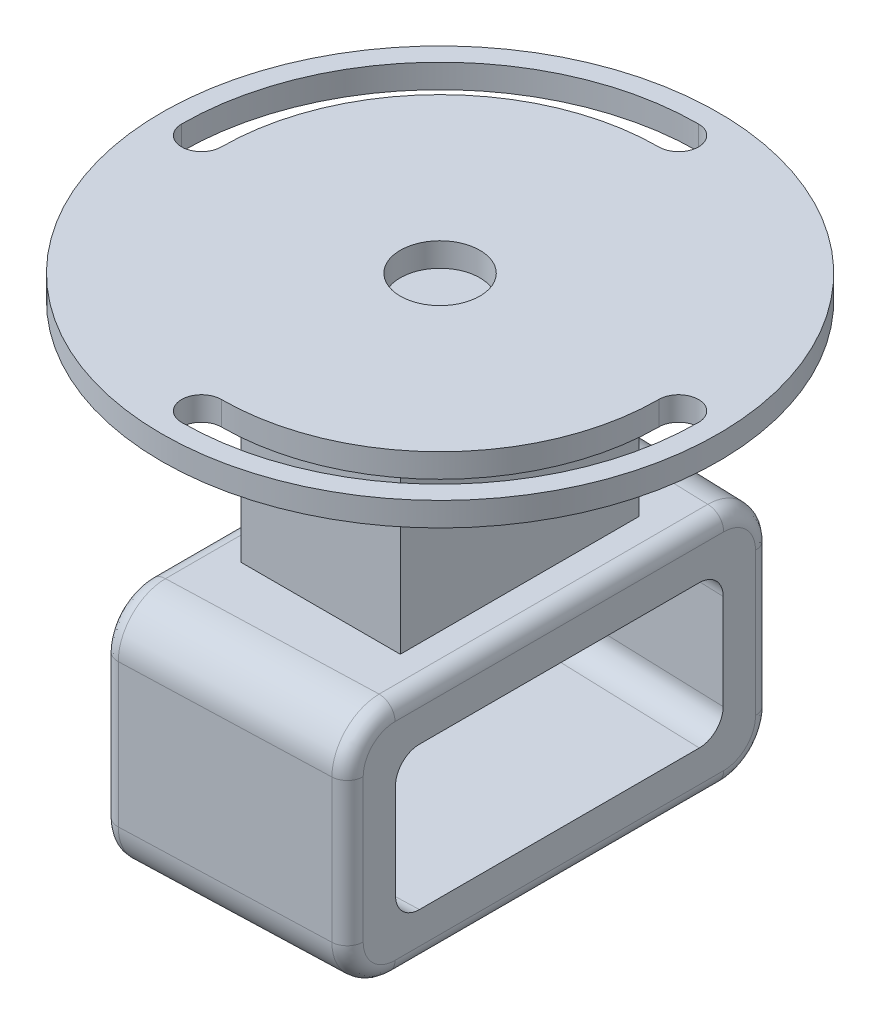
SolidWorks part; units mm, degrees
ref_plane "정면" through (0, 0, 0) normal (0, 0, 1) x (1, 0, 0)
ref_plane "윗면" through (0, 0, 0) normal (0, 1, 0) x (1, 0, 0)
ref_plane "우측면" through (0, 0, 0) normal (1, 0, 0) x (0, 0, -1)
sketch "스케치1" plane through (0, 0, 0) normal (0, 1, 0) x (1, 0, 0)
  circle A0 centre (0, 0) radius 35
  circle A1 centre (0, 0) radius 32.5 construction
  circle A2 centre (0, 0) radius 27.5 construction
  circle A3 centre (0, 0) radius 30 construction
  arc A4 (0, 27.5) -> (0, 32.5) centre (0, 30) ccw
  arc A5 (32.5, 0) -> (27.5, 0) centre (30, 0) ccw
  arc A6 (0, -27.5) -> (0, -32.5) centre (0, -30) ccw
  arc A7 (-32.5, 0) -> (-27.5, 0) centre (-30, 0) ccw
  arc A8 (-27.5, 0) -> (0, 27.5) centre (0, 0) cw
  arc A9 (-32.5, 0) -> (0, 32.5) centre (0, 0) cw
  arc A10 (0, -27.5) -> (27.5, 0) centre (0, 0) ccw
  arc A11 (0, -32.5) -> (32.5, 0) centre (0, 0) ccw
  circle A12 centre (0, 0) radius 5
  dimension "D1" = 70
  dimension "D2" = 65
  dimension "D3" = 60
  dimension "D4" = 55
  dimension "D5" = 10
extrude "보스-돌출1" add sketch "스케치1" along normal blind 3
sketch "스케치2" plane through (0, 0, 0) normal (0, -1, 0) x (1, 0, 0)
  line L1 (-10, -15) -> (10, -15)
  line L2 (-10, -15) -> (-10, 15)
  line L3 (-10, 15) -> (10, 15)
  line L4 (10, -15) -> (10, 15)
  line L5 (-10, -15) -> (10, 15) construction
  line L6 (-10, 15) -> (10, -15) construction
  point P0 (0, 0)
  dimension "D1" = 20
  dimension "D2" = 30
extrude "보스-돌출2" add sketch "스케치2" along normal blind 26
sketch "스케치5" plane through (0, -26, 0) normal (0, -1, 0) x (1, 0, 0)
  line L0 (15, 20.6) -> (15, -20.6)
  line L2 (15, -20.6) -> (-15, -21.6)
  line L3 (-15, -21.6) -> (-15, 21.6)
  line L4 (-15, 21.6) -> (15, 20.6)
  line L5 (15, 0) -> (-15, 0) construction
  line L6 (10, 15) -> (-10, 15) construction
  line L7 (10, -15) -> (10, 15) construction
  line L9 (-10, 15) -> (-10, -15) construction
  point P2 (11.7784, -18.4311)
  point P8 (-16.388, -24.8863)
  point P9 (-24.0486, -22.3046)
  point P10 (0, 0)
  point P14 (-16.0731, -21.6)
  point P18 (0, 0)
  dimension "D1" = 41.2
  dimension "D2" = 43.2
  dimension "D3" = 15
  dimension "D4" = 30
  dimension "D5" = 10
extrude "보스-돌출4" add sketch "스케치5" along normal blind 6
sketch "스케치6" plane through (0, -26, 0) normal (0, 1, 0) x (1, 0, 0)
  line L0 (-15, -21.6) -> (-15, -27.6)
  line L1 (-15, -27.6) -> (15, -26.6)
  line L2 (15, -26.6) -> (15, -20.6)
  line L3 (15, -20.6) -> (-15, -21.6)
  line L4 (-15, 21.6) -> (-15, 27.6)
  line L5 (-15, 27.6) -> (15, 26.6)
  line L6 (15, 26.6) -> (15, 20.6)
  line L7 (15, 20.6) -> (-15, 21.6)
  line L8 (-15, 21.6) -> (15, 20.6) construction
  line L9 (15, 20.6) -> (15, -20.6) construction
  dimension "D1" = 6
  dimension "D2" = 6
  dimension "D3" = 6
  dimension "D4" = 6
extrude "보스-돌출5" add sketch "스케치6" against normal blind 30
extrude "보스-돌출6" add sketch "스케치5<2>" against normal blind 6 from surface starting at face at (0, -56, 24.1)
sketch "스케치5<2>" plane through (0, -26, 0) normal (0, -1, 0) x (1, 0, 0) same geometry as "스케치5"
fillet "필렛1" radius 3 4 edges at (0, -32, -21.1) (0, -50, -21.1) (0, -50, 21.1) (0, -32, 21.1)
fillet "필렛2" radius 6 4 edges at (0, -26, 27.1) (0, -26, -27.1) (0, -56, -27.1) (0, -56, 27.1)
fillet "필렛3" radius 2 16 edges at (15, -54.2426, 24.8417) (15, -41, 26.6) (15, -27.7574, 24.8417) (15, -26, 0) (15, -27.7574, -24.8417) (15, -41, -26.6) (15, -54.2426, -24.8417) (-15, -54.2426, -25.8417) (-15, -41, -27.6) (-15, -27.7574, -25.8417) (-15, -26, 0) (-15, -27.7574, 25.8417) (-15, -41, 27.6) (-15, -54.2426, 25.8417) (15, -56, 0) (-15, -56, 0)
